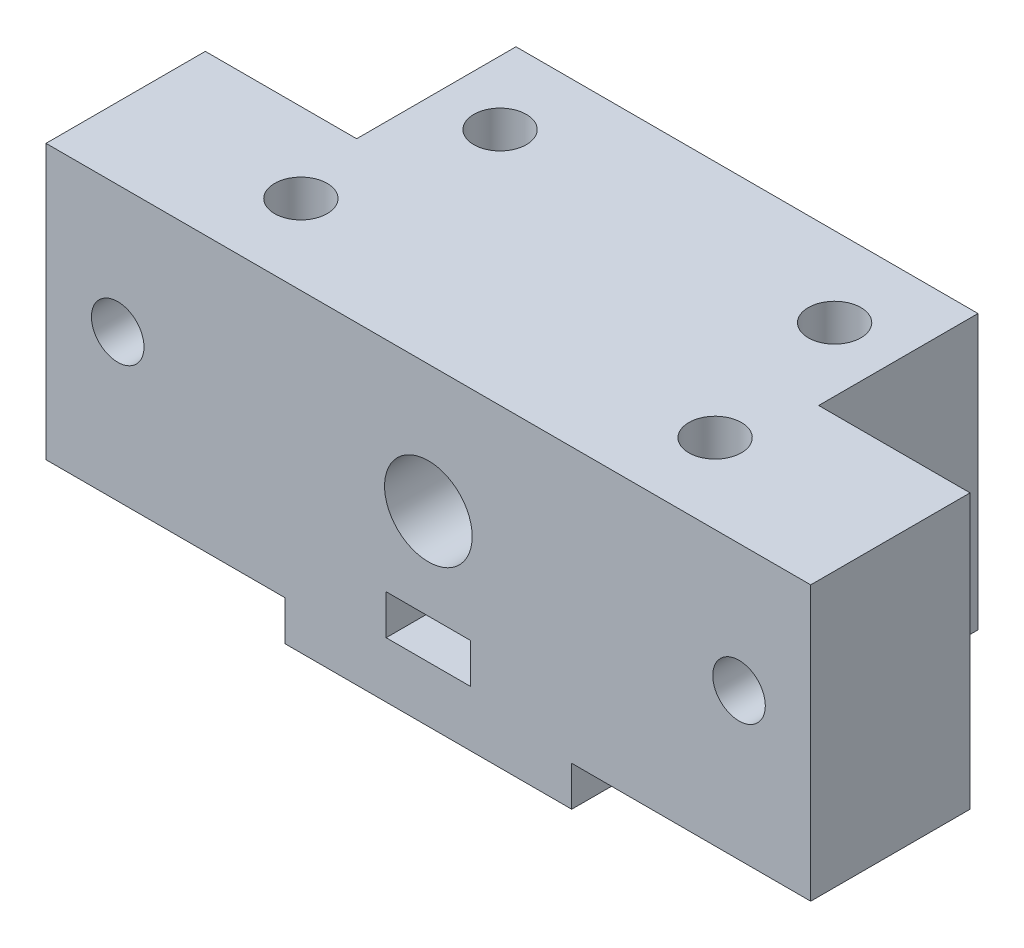
SolidWorks part; units mm, degrees
ref_plane "Płaszczyzna przednia" through (0, 0, 0) normal (0, 0, 1) x (1, 0, 0)
ref_plane "Płaszczyzna górna" through (0, 0, 0) normal (0, 1, 0) x (1, 0, 0)
ref_plane "Płaszczyzna prawa" through (0, 0, 0) normal (1, 0, 0) x (0, 0, -1)
sketch "Szkic1" plane through (0, 0, 0) normal (0, 0, 1) x (1, 0, 0)
  line L1 (-24, 8.6) -> (24, 8.6)
  line L2 (-24, 8.6) -> (-24, -8.6)
  line L3 (-24, -8.6) -> (24, -8.6)
  line L4 (24, 8.6) -> (24, -8.6)
  line L5 (-24, 8.6) -> (24, -8.6) construction
  line L6 (-24, -8.6) -> (24, 8.6) construction
  point P0 (0, 0)
  dimension "D1" = 48
  dimension "D2" = 17.2
extrude "Dodanie-wyciągnięcie1" add sketch "Szkic1" along normal blind 10
sketch "Szkic2" plane through (0, 0, 10) normal (0, 0, 1) x (1, 0, 0)
  line L0 (-19.5, 8.6) -> (-19.5, -8.6) construction
  line L1 (24, 8.6) -> (-24, 8.6) construction
  line L2 (-24, -8.6) -> (24, -8.6) construction
  line L3 (-24, 8.6) -> (-24, -8.6) construction
  line L4 (-24, 0.6) -> (24, 0.6) construction
  line L5 (24, -8.6) -> (24, 8.6) construction
  line L6 (19.5, 8.6) -> (19.5, -8.6) construction
  circle A2 centre (-19.5, 0.6) radius 1.65
  circle A3 centre (19.5, 0.6) radius 1.65
  dimension "D2" = 8
  dimension "D1" = 4.5
  dimension "D3" = 4.5
extrude "Wytnij-wyciągnięcie1" cut sketch "Szkic2" against normal blind 10
sketch "Szkic3" plane through (0, 0, 10) normal (0, 0, 1) x (1, 0, 0)
  line L0 (-17.85, 0.6) -> (17.85, 0.6) construction
  circle A0 centre (-19.5, 0.6) radius 1.65 construction
  circle A1 centre (19.5, 0.6) radius 1.65 construction
  circle A2 centre (0, 0.6) radius 2.75
  dimension "D1" = 5.5
extrude "Wytnij-wyciągnięcie2" cut sketch "Szkic3" against normal up to surface (10 mm away) contours A2 up to face at (-17.85, 0.6, 0)
sketch "Szkic4" plane through (0, -8.6, 0) normal (0, -1, 0) x (1, 0, 0)
  line L0 (-24, 5) -> (24, 5) construction
  line L1 (-24, 10) -> (-24, 0) construction
  line L2 (24, 10) -> (24, 0) construction
  line L3 (-24, 10) -> (24, 10) construction
  circle A0 centre (-13, 5) radius 1.65
  circle A1 centre (13, 5) radius 1.65
  dimension "D4" = 3.3
  dimension "D5" = 3.3
  dimension "D1" = 5
  dimension "D2" = 11
  dimension "D3" = 11
extrude "Wytnij-wyciągnięcie3" cut sketch "Szkic4" against normal up to surface (17.2 mm away) up to face at (0, 8.6, 5)
sketch "Szkic5" plane through (0, 0, 0) normal (0, 0, -1) x (-1, 0, 0)
  line L0 (-24, 8.6) -> (24, 8.6) construction
  line L1 (-14.5, 8.6) -> (14.5, 8.6)
  line L2 (-14.5, 8.6) -> (-14.5, -8.6)
  line L3 (-14.5, -8.6) -> (14.5, -8.6)
  line L4 (14.5, 8.6) -> (14.5, -8.6)
  line L5 (24, -8.6) -> (-24, -8.6) construction
  line L6 (-24, -8.6) -> (-24, 8.6) construction
  line L7 (24, 8.6) -> (24, -8.6) construction
  circle A0 centre (0, 0.6) radius 2.75
  dimension "D1" = 9.5
  dimension "D2" = 9.5
extrude "Dodanie-wyciągnięcie2" add sketch "Szkic5" along normal blind 10
sketch "Szkic6" plane through (0, 8.6, 0) normal (0, 1, 0) x (1, 0, 0)
  line L0 (-14.5, 5) -> (14.5, 5) construction
  line L1 (-14.5, 10) -> (-14.5, 0) construction
  line L2 (14.5, 10) -> (14.5, 0) construction
  line L3 (-14.5, 10) -> (14.5, 10) construction
  circle A0 centre (-10.5, 5) radius 1.65
  circle A1 centre (10.5, 5) radius 1.65
  dimension "D2" = 4
  dimension "D4" = 3.3
  dimension "D1" = 5
  dimension "D3" = 4
extrude "Wytnij-wyciągnięcie4" cut sketch "Szkic6" against normal up to surface (17.2 mm away) contours A1 | A0 up to face at (-13, -8.6, 3.35)
sketch "Szkic7" plane through (0, 0, -10) normal (0, 0, -1) x (-1, 0, 0)
  line L0 (-14.5, -8.6) -> (14.5, -8.6) construction
  line L1 (-7.5, -13.5796) -> (7.5, -13.5796)
  line L2 (-7.5, -13.5796) -> (-7.5, -3.6204)
  line L3 (-7.5, -3.6204) -> (7.5, -3.6204)
  line L4 (7.5, -13.5796) -> (7.5, -3.6204)
  line L5 (-7.5, -13.5796) -> (7.5, -3.6204) construction
  line L6 (-7.5, -3.6204) -> (7.5, -13.5796) construction
  point P0 (0, -8.6)
  dimension "D1" = 15
extrude "Wytnij-wyciągnięcie5" cut sketch "Szkic7" against normal blind 0.1
chamfer "Sfazowanie1" distance 5 angle 45 1 edges at (0, -8.6, -9.9)
sketch "Szkic8" plane through (0, -8.6, 0) normal (0, -1, 0) x (1, 0, 0)
  line L0 (-24, 10) -> (24, 10) construction
  line L1 (-9, 0) -> (9, 0)
  line L2 (-9, 0) -> (-9, 10)
  line L3 (-9, 10) -> (9, 10)
  line L4 (9, 0) -> (9, 10)
  line L5 (-9, 0) -> (9, 10) construction
  line L6 (-9, 10) -> (9, 0) construction
  line L7 (-7.5, -4.9) -> (7.5, -4.9) construction
  point P0 (0, 5)
  point P9 (0, -4.9)
  dimension "D1" = 18
  dimension "D2" = 0
  dimension "D3" = 10
sketch "Szkic9" plane through (0, -8.6, 0) normal (0, -1, 0) x (1, 0, 0)
  circle A0 centre (0, 5) radius 1.5
  dimension "D1" = 3
extrude "Wytnij-wyciągnięcie6" cut sketch "Szkic9" against normal blind 10
sketch "Szkic10" plane through (0, -8.6, 0) normal (0, -1, 0) x (1, 0, 0)
  line L0 (-2.65, 6.53) -> (-2.65, 10)
  line L2 (-2.65, 6.53) -> (-2.65, 3.47)
  line L3 (-2.65, 3.47) -> (0, 1.94)
  line L4 (0, 1.94) -> (2.65, 3.47)
  line L5 (2.65, 3.47) -> (2.65, 6.53)
  line L7 (-9, 10) -> (9, 10) construction
  line L8 (-2.65, 10) -> (2.65, 10)
  line L9 (2.65, 10) -> (2.65, 6.53)
  line L11 (-1.325, 7.295) -> (-2.65, 6.53) [skipped]
  line L12 (2.65, 6.53) -> (1.325, 7.295) [skipped]
  circle A0 centre (0, 5) radius 2.65 construction
  dimension "D1" = 5.3
extrude "Wytnij-wyciągnięcie7" cut sketch "Szkic10" against normal blind 3.5
extrude "Dodanie-wyciągnięcie3" add sketch "Szkic8" along normal blind 2.5 and the other way blind 1
sketch "Szkic11" plane through (0, -5.1, 0) normal (0, -1, 0) x (1, 0, 0)
  circle A0 centre (0, 5) radius 1.5
extrude "Wytnij-wyciągnięcie8" cut sketch "Szkic11" along normal blind 7.5
